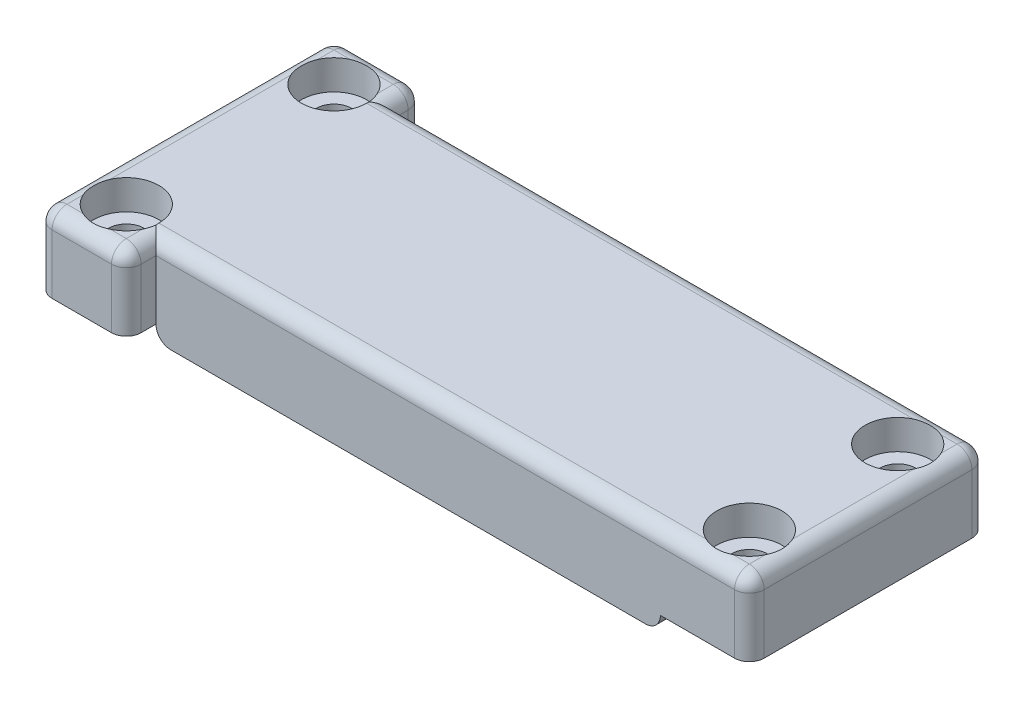
SolidWorks part; units mm, degrees
material "ABS PC"
ref_plane "前基準面" through (0, 0, 0) normal (0, 0, 1) x (1, 0, 0)
ref_plane "上基準面" through (0, 0, 0) normal (0, 1, 0) x (1, 0, 0)
ref_plane "右基準面" through (0, 0, 0) normal (1, 0, 0) x (0, 0, -1)
sketch "草圖1" plane through (0, 0, 0) normal (0, 1, 0) x (1, 0, 0)
  line L0 (0, 0) -> (-20, 0) construction
  line L1 (-20, -8) -> (20, -8)
  line L2 (-20, -4) -> (-20, 4)
  line L3 (-20, 8) -> (20, 8)
  line L4 (20, -8) -> (20, 8)
  line L5 (-20, 4) -> (-26, 4)
  line L6 (-26, 4) -> (-26, 10)
  line L7 (-26, 10) -> (-20, 10)
  line L8 (-20, 10) -> (-20, 8)
  line L9 (-20, -10) -> (-20, -8)
  line L10 (-26, -10) -> (-20, -10)
  line L11 (-26, -4) -> (-26, -10)
  line L12 (-20, -4) -> (-26, -4)
  dimension "D1" = 16
  dimension "D3" = 20
  dimension "D4" = 40
extrude "填料-伸長1" add sketch "草圖1" along normal blind 6
sketch "草圖2" plane through (0, 0, 0) normal (0, 1, 0) x (1, 0, 0)
  line L1 (-26, 4) -> (-20, 4)
  line L2 (-26, 4) -> (-26, -4)
  line L3 (-26, -4) -> (-20, -4)
  line L4 (-20, 4) -> (-20, -4)
extrude "填料-伸長2" add sketch "草圖2" along normal blind 4 from offset 2
fillet "圓角7" radius 1 1 edges at (-20, 2, 0)
sketch "草圖3" plane through (0, 0, 0) normal (0, -1, 0) x (-1, 0, 0)
  line L4 (-20, 8) -> (-14, 8)
  line L5 (-20, 8) -> (-20, -8)
  line L6 (-20, -8) -> (-14, -8)
  line L7 (-14, 8) -> (-14, -8)
  dimension "D1" = 6
  dimension "D2" = 16
extrude "除料-伸長1" cut sketch "草圖3" against normal blind 1
sketch "草圖4" plane through (0, 0, 0) normal (0, 1, 0) x (1, 0, 0)
  line L0 (-20, 0) -> (0, 0) construction
  circle A0 centre (-23, 7) radius 2.2
  circle A1 centre (-23, -7) radius 2.2
  circle A2 centre (17, 5) radius 2.2
  circle A3 centre (17, -5) radius 2.2
extrude "除料-伸長2" cut sketch "草圖4" along normal blind 2 from offset 4
sketch "草圖5" plane through (0, 4, 0) normal (0, 1, 0) x (1, 0, 0)
  circle A0 centre (-23, 7) radius 1.2
  circle A1 centre (-23, -7) radius 1.2
  circle A2 centre (17, 5) radius 1.2
  circle A3 centre (17, -5) radius 1.2
  dimension "D1" = 14
  dimension "D2" = 10
extrude "除料-伸長3" cut sketch "草圖5" against normal blind 3
fillet "圓角8" radius 1 2 edges at (0, 6, -8) (0, 6, 8)
fillet "圓角9" radius 1 5 edges at (20, 3, 8) (20, 5.7071, 7.7071) (20, 3, -8) (20, 5.7071, -7.7071) (20, 6, 0)
fillet "圓角10" radius 1 1 edges at (-20, 6, -8.5)
fillet "圓角11" radius 1 1 edges at (-20, 6, 8.5)
fillet "圓角12" radius 1 6 edges at (-23.5, 6, -10) (-20.2929, 5.7071, -10) (-23.5, 6, 10) (-20.2929, 5.7071, 10) (-20, 2.5, -10) (-20, 2.5, 10)
fillet "圓角13" radius 1 5 edges at (-26, 5.7071, 9.7071) (-26, 6, 0) (-26, 5.7071, -9.7071) (-26, 2.5, 10) (-26, 2.5, -10)
sketch "草圖6" plane through (0, 0, 0) normal (0, 1, 0) x (1, 0, 0)
  line L1 (-20, -10) -> (-26, -10)
  line L2 (-20, -10) -> (-20, 10)
  line L3 (-20, 10) -> (-26, 10)
  line L4 (-26, -10) -> (-26, 10)
extrude "除料-伸長4" cut sketch "草圖6" along normal blind 1
fillet "圓角14" radius 1 2 edges at (-20, 0, 0) (14, 0, 0)
